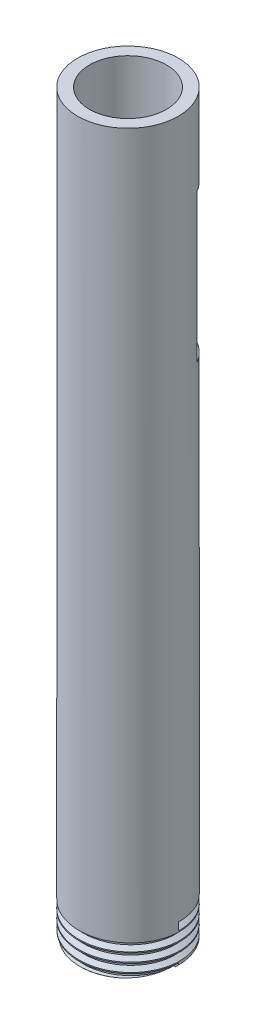
SolidWorks part; units mm, degrees
ref_plane "Front Plane" through (0, 0, 0) normal (0, 0, 1) x (1, 0, 0)
ref_plane "Top Plane" through (0, 0, 0) normal (0, 1, 0) x (1, 0, 0)
ref_plane "Right Plane" through (0, 0, 0) normal (1, 0, 0) x (0, 0, -1)
sketch "Sketch1" plane through (0, 0, 0) normal (0, 1, 0) x (1, 0, 0)
  circle A0 centre (0, 0) radius 17
  circle A1 centre (0, 0) radius 13
  dimension "D1" = 34
  dimension "D2" = 26
extrude "Boss-Extrude1" add sketch "Sketch1" along normal mid plane 249
ref_plane "Plane1" through (0, 87, 0) normal (0, 1, 0) x (1, 0, 0)
sketch "Sketch3" plane through (0, 87, 0) normal (0, 1, 0) x (1, 0, 0)
  line L0 (0, 0) -> (14.7224, 8.5)
  line L1 (0, 0) -> (-14.7224, 8.5)
  line L2 (-14.7224, 8.5) -> (14.7224, 8.5) construction
  arc A0 (14.7224, 8.5) -> (-14.7224, 8.5) centre (0, 0) ccw
  circle A1 centre (0, 0) radius 17 construction
  dimension "D1" = 120
extrude "Cut-Extrude2" cut sketch "Sketch3" against normal blind 50 from offset 10
sketch "Sketch6" plane through (0, -124.5, 0) normal (0, -1, 0) x (1, 0, 0)
  circle A0 centre (0, 0) radius 17
thread "Thread1" start angle 0, offset 1, length 12, pitch 3, diameter 34
ref_plane "Plane2" through (17, -125.5, 0) normal (0, 0, 1) x (1, 0, 0)
sketch "Thread Profile1" plane through (17, -125.5, 0) normal (0, 0, 1) x (1, 0, 0)
  line L0 (0, 0) -> (0, 3) construction
  line L11 (0, 0) -> (0, 2.625)
  line L12 (0, 2.625) -> (-1.6238, 1.6875)
  line L13 (-1.6238, 1.6875) -> (-1.6238, 0.9375)
  line L15 (-1.6238, 0.9375) -> (0, 0)
  line L17 (-1.6238, 1.3125) -> (0, 1.3125) construction
  point P2 (0, 0)
  dimension "Pitch" = 3
  dimension "Profile_Angle" = 60
  dimension "Profile_Land" = 0.75
  dimension "Profile_Height" = 1.6238
chamfer "Chamfer2" distance 1 angle 45 1 edges
sketch "Sketch7" plane through (0, 124.5, 0) normal (0, 1, 0) x (1, 0, 0)
  line L0 (-13, 0) -> (13, 0) construction
  circle A0 centre (0, 0) radius 13 construction
